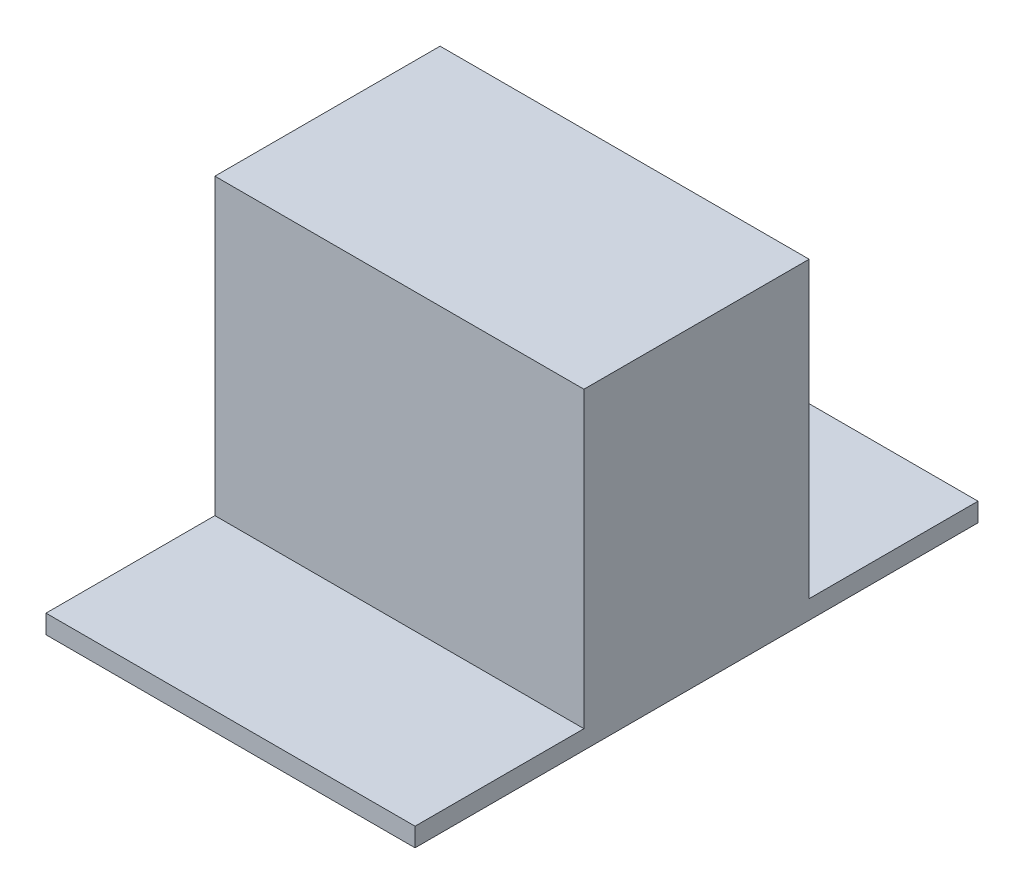
SolidWorks part; units mm, degrees
ref_plane "Front" through (0, 0, 0) normal (0, 0, 1) x (1, 0, 0)
ref_plane "Top" through (0, 0, 0) normal (0, 1, 0) x (1, 0, 0)
ref_plane "Right" through (0, 0, 0) normal (1, 0, 0) x (0, 0, -1)
sketch "Esquisse1" plane through (0, 0, 0) normal (0, 0, 1) x (1, 0, 0)
  line L1 (0, 0) -> (590, 0)
  line L2 (0, 0) -> (0, 500)
  line L3 (0, 500) -> (590, 500)
  line L4 (590, 0) -> (590, 500)
  dimension "D1" = 590
  dimension "D2" = 500
extrude "Boss.-Extru.1" add sketch "Esquisse1" along normal blind 360
sketch "Esquisse2" plane through (0, 0, 0) normal (0, -1, 0) x (1, 0, 0)
  line L0 (295, 180) -> (295, 360) construction
  line L1 (30, 0) -> (560, 0)
  line L2 (30, 0) -> (30, 360)
  line L3 (30, 360) -> (560, 360)
  line L4 (560, 0) -> (560, 360)
  line L5 (30, 0) -> (560, 360) construction
  line L6 (30, 360) -> (560, 0) construction
  line L7 (0, 360) -> (590, 360) construction
  line L8 (0, 180) -> (295, 180) construction
  line L9 (0, 360) -> (0, 0) construction
  point P0 (295, 180)
  dimension "D1" = 530
  dimension "D2" = 360
extrude "Boss.-Extru.2" add sketch "Esquisse2" along normal blind 10
sketch "Esquisse3" plane through (0, -10, 0) normal (0, -1, 0) x (1, 0, 0)
  line L0 (295, 360) -> (295, 180) construction
  line L1 (75, 347.5) -> (515, 347.5) construction
  line L2 (75, 347.5) -> (75, 12.5) construction
  line L3 (75, 12.5) -> (515, 12.5) construction
  line L4 (515, 347.5) -> (515, 12.5) construction
  line L5 (75, 347.5) -> (515, 12.5) construction
  line L6 (75, 12.5) -> (515, 347.5) construction
  line L7 (560, 360) -> (30, 360) construction
  line L8 (295, 180) -> (30, 180) construction
  line L9 (30, 360) -> (30, 0) construction
  circle A0 centre (75, 12.5) radius 4
  circle A1 centre (515, 12.5) radius 4
  circle A2 centre (515, 347.5) radius 4
  circle A3 centre (75, 347.5) radius 4
  point P0 (295, 180)
  dimension "D1" = 8
  dimension "D2" = 440
  dimension "D3" = 335
extrude "Enlèv. mat.-Extru.1" cut sketch "Esquisse3" against normal blind 10
sketch "Esquisse4" plane through (0, 0, 360) normal (0, 0, 1) x (1, 0, 0)
  line L0 (0, 500) -> (0, 0) construction
  line L1 (590, 0) -> (0, 0)
  line L2 (590, 0) -> (590, 30)
  line L3 (590, 30) -> (0, 30)
  line L4 (0, 0) -> (0, 30)
  dimension "D1" = 30
extrude "Boss.-Extru.3" add sketch "Esquisse4" along normal blind 270
extrude "Boss.-Extru.4" add sketch "Esquisse4<2>" against normal blind 270 from vertex starting at point (0, 590, 0)
sketch "Esquisse4<2>" plane through (0, 0, 360) normal (0, 0, 1) x (1, 0, 0) same geometry as "Esquisse4"
